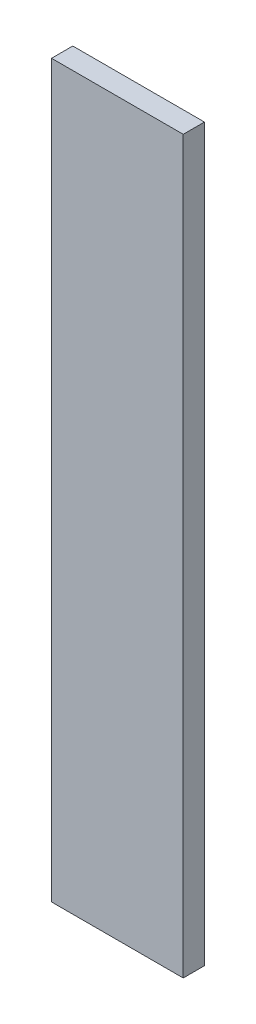
SolidWorks part; units mm, degrees
ref_plane "Front Plane" through (0, 0, 0) normal (0, 0, 1) x (1, 0, 0)
ref_plane "Top Plane" through (0, 0, 0) normal (0, 1, 0) x (1, 0, 0)
ref_plane "Right Plane" through (0, 0, 0) normal (1, 0, 0) x (0, 0, -1)
sketch "Sketch1" plane through (0, 0, 0) normal (0, 0, 1) x (1, 0, 0)
  line L1 (0, 0) -> (860, 0)
  line L2 (0, 0) -> (0, 155)
  line L3 (0, 155) -> (860, 155)
  line L4 (860, 0) -> (860, 155)
  dimension "D1" = 860
  dimension "D2" = 155
extrude "Boss-Extrude1" add sketch "Sketch1" along normal blind 25
ref_axis "Axis1" through (0, 77.5, 25) along (1, 0, 0)
sketch "Sketch2" plane through (0, 0, 25) normal (0, 0, 1) x (1, 0, 0)
  line L1 (0, 155) -> (0, 0) construction
  line L2 (860, 0) -> (860, 155) construction
  point P0 (10, 10)
  point P5 (870, 850)
  line B0 (75.884, 666.3249) -> (69.1154, 198.6756)
  line B1 (56.3998, 41.0836) -> (14.64, 177.6737)
  line B2 (19.789, 666.3249) -> (26.5001, 202.6475)
  line B3 (79.042, 193.5314) -> (85.8106, 661.1807)
  line B4 (98.5261, 818.7727) -> (140.2859, 682.1826)
  line B5 (135.1369, 193.5314) -> (128.4258, 657.2088)
  arc B6 (70.6766, 672.6633) -> (47.8365, 674.734) centre (47.8365, 547.734) ccw
  arc B7 (75.884, 666.3249) -> (70.6766, 672.6633) centre (69.5346, 666.4168) ccw
  arc B8 (69.1154, 198.6756) -> (93.6811, 159.9487) centre (112.2198, 198.8633) ccw
  arc B9 (94.5833, 158.6394) -> (93.6811, 159.9487) centre (93.0007, 158.5144) ccw
  arc B10 (90.4571, 113.7859) -> (94.5833, 158.6394) centre (-37.7274, 148.1945) ccw
  arc B11 (90.4571, 113.7859) -> (86.3663, 79.1275) centre (210.9521, 81.9932) ccw
  arc B12 (86.3663, 79.1275) -> (90.5165, 73.3161) centre (92.7147, 79.2735) ccw
  arc B13 (56.3998, 41.0836) -> (90.5165, 73.3161) centre (81.449, 48.7419) ccw
  circle B14 centre (64.6941, 53.0484) radius 4.7625
  circle B15 centre (57.9511, 75.1038) radius 4.7625
  circle B16 centre (51.208, 97.1593) radius 4.7625
  circle B17 centre (44.465, 119.2147) radius 4.7625
  circle B18 centre (37.722, 141.2702) radius 4.7625
  circle B19 centre (30.9789, 163.3256) radius 4.7625
  arc B20 (19.3865, 190.3517) -> (14.64, 177.6737) centre (25.267, 180.9227) ccw
  arc B21 (19.3865, 190.3517) -> (26.5001, 202.6475) centre (10.7817, 203.5356) ccw
  arc B22 (24.9964, 672.6633) -> (19.789, 666.3249) centre (26.1384, 666.4168) ccw
  arc B23 (47.8365, 674.734) -> (24.9964, 672.6633) centre (47.8365, 547.734) ccw
  arc B24 (84.2493, 187.193) -> (107.0895, 185.1223) centre (107.0895, 312.1223) ccw
  arc B25 (79.042, 193.5314) -> (84.2493, 187.193) centre (85.3913, 193.4395) ccw
  arc B26 (85.8106, 661.1807) -> (61.2448, 699.9076) centre (42.7062, 660.993) ccw
  arc B27 (60.3427, 701.2169) -> (61.2448, 699.9076) centre (61.9253, 701.3419) ccw
  arc B28 (64.4689, 746.0704) -> (60.3427, 701.2169) centre (192.6534, 711.6618) ccw
  arc B29 (64.4689, 746.0704) -> (68.5596, 780.7288) centre (-56.0262, 777.8631) ccw
  arc B30 (68.5596, 780.7288) -> (64.4095, 786.5402) centre (62.2113, 780.5828) ccw
  arc B31 (98.5261, 818.7727) -> (64.4095, 786.5402) centre (73.4769, 811.1144) ccw
  circle B32 centre (90.3053, 806.9521) radius 4.7625
  circle B33 centre (97.0483, 784.8967) radius 4.7625
  circle B34 centre (103.7914, 762.8412) radius 4.7625
  circle B35 centre (110.5344, 740.7858) radius 4.7625
  circle B36 centre (117.2774, 718.7303) radius 4.7625
  circle B37 centre (124.0204, 696.6749) radius 4.7625
  arc B38 (135.5395, 669.5045) -> (140.2859, 682.1826) centre (129.659, 678.9336) ccw
  arc B39 (135.5395, 669.5045) -> (128.4258, 657.2088) centre (144.1442, 656.3206) ccw
  arc B40 (129.9296, 187.193) -> (135.1369, 193.5314) centre (128.7876, 193.4395) ccw
  arc B41 (107.0895, 185.1223) -> (129.9296, 187.193) centre (107.0895, 312.1223) ccw
  dimension "D1" = 10
  dimension "D2" = 10
sketch_block_instance "Block3-1"
sketch_block "Block3" parameters "D1"=5, "D2"=10
ref_axis "Axis2" through (430, 155, 0) along (0, -0.9872, 0.1592)
ref_axis "Axis4" through (10, 10, 25) along (0, 0, -1)
ref_axis "Axis5" through (870, 850, 25) along (0, 0, -1)
move or copy body "Body-Move/Copy2" bodies to move or copy 101 copy no rotation origin (0, 0, 0) rotation axis (0, 0, 1) rotation angle 90
move or copy body "Body-Move/Copy3" bodies to move or copy 103 copy no translate (155, 0, 0)
